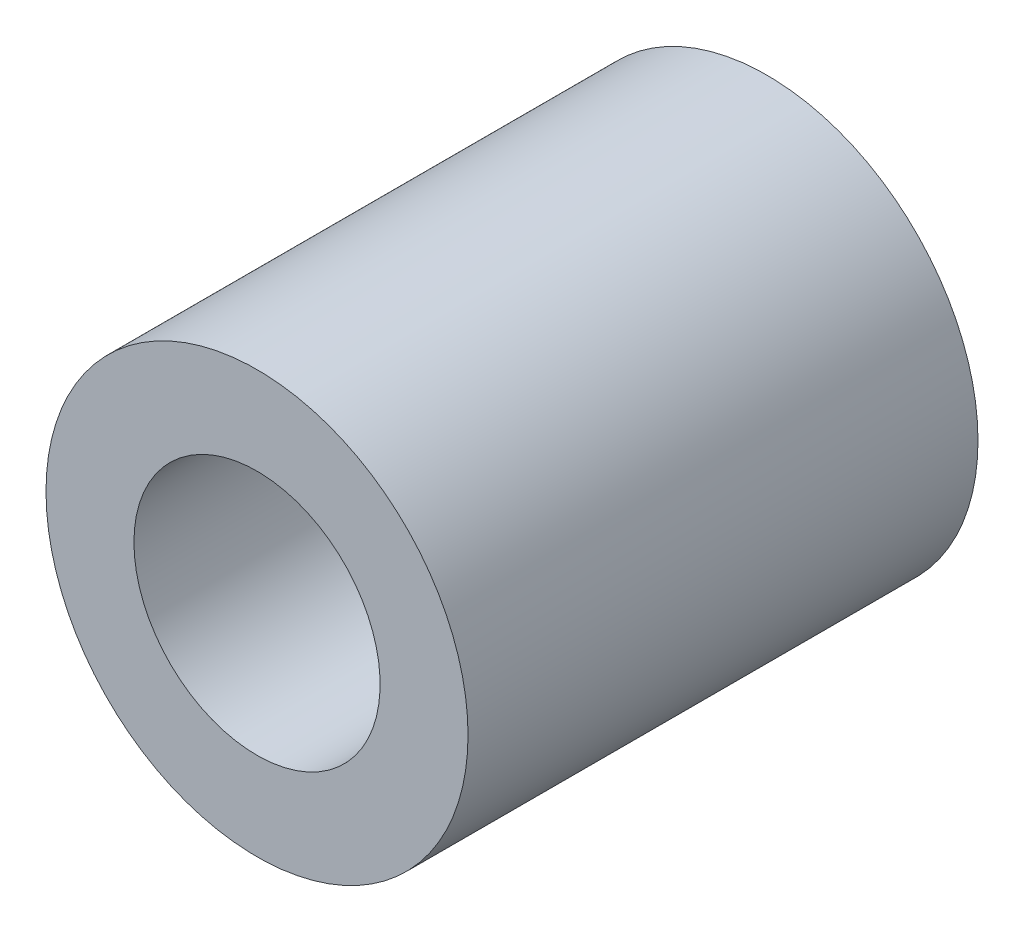
SolidWorks part; units mm, degrees
ref_plane "前视基准面" through (0, 0, 0) normal (0, 0, 1) x (1, 0, 0)
ref_plane "上视基准面" through (0, 0, 0) normal (0, 1, 0) x (1, 0, 0)
ref_plane "右视基准面" through (0, 0, 0) normal (1, 0, 0) x (0, 0, -1)
sketch "草图1" plane through (0, 0, 0) normal (0, 0, 1) x (1, 0, 0)
  circle A0 centre (0, 0) radius 3.5
  circle A1 centre (0, 0) radius 6
extrude "凸台-拉伸1" add sketch "草图1" along normal blind 14.5
